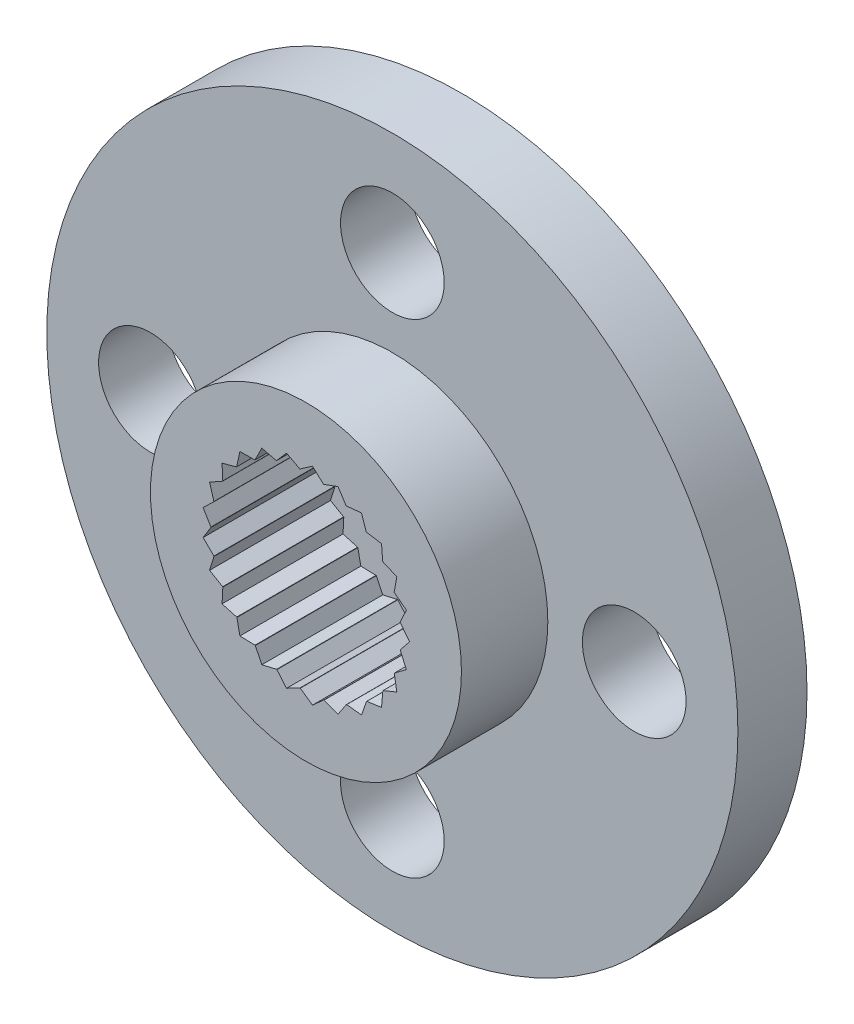
SolidWorks part; units mm, degrees
ref_plane "Front Plane" through (0, 0, 0) normal (0, 0, 1) x (1, 0, 0)
ref_plane "Top Plane" through (0, 0, 0) normal (0, 1, 0) x (1, 0, 0)
ref_plane "Right Plane" through (0, 0, 0) normal (1, 0, 0) x (0, 0, -1)
sketch "Sketch1" plane through (0, 0, 0) normal (0, 0, 1) x (1, 0, 0)
  circle A0 centre (0, 0) radius 10
  circle A1 centre (0, 0) radius 7 construction
  circle A2 centre (0, 7) radius 1.5
  circle A3 centre (7, 0) radius 1.5
  circle A4 centre (0, -7) radius 1.5
  circle A5 centre (-7, 0) radius 1.5
  circle A6 centre (0, 0) radius 4.5
  dimension "D1" = 20
  dimension "D2" = 3
  dimension "D3" = 4
extrude "Boss-Extrude1" add sketch "Sketch1" along normal blind 2
extrude "Boss-Extrude2" add sketch "Sketch1<2>" along normal blind 4.5 contours A6 region at (0, 0, 0)
sketch "Sketch1<2>" plane through (0, 0, 0) normal (0, 0, 1) x (1, 0, 0) same geometry as "Sketch1"
sketch "Sketch2" plane through (0, 0, 0) normal (0, 0, -1) x (-1, 0, 0)
  circle A0 centre (0, 0) radius 1.5
extrude "Cut-Extrude1" cut sketch "Sketch2" against normal blind 4.5
sketch "Sketch3" plane through (0, 0, 4.5) normal (0, 0, 1) x (1, 0, 0)
  circle A0 centre (0, 0) radius 2.75
extrude "Cut-Extrude2" cut sketch "Sketch3" against normal blind 3.5
sketch "Sketch4" plane through (0, 0, 4.5) normal (0, 0, 1) x (1, 0, 0)
  line L0 (0, 0) -> (-3, 0)
  line L1 (0, 0) -> (-2.9763, 0.376)
  line L2 (0, 0) -> (-2.9083, 0.7359)
  line L3 (-2.75, 0) -> (-2.9763, 0.376)
  line L4 (-2.666, 0.6746) -> (-2.9763, 0.376)
  circle A0 centre (0, 0) radius 3
  circle A1 centre (0, 0) radius 2.75 construction
  circle A2 centre (0, 0) radius 2.75 construction
  circle A3 centre (0, 0) radius 2.75
  circle M6 centre (0, 0) radius 2.75
  dimension "D1" = 7.2
  dimension "D2" = 14.2
extrude "Cut-Extrude3" cut sketch "Sketch4" against normal blind 3.5 contours L4 L1 M6 | L3 L1 M6 region at (-2.8205, 0.2422, 4.5) region at (-2.7928, 0.4638, 4.5)
pattern_circular "CirPattern1" count 25 over 360 about axis through (0, 0, 4.5) along (0, 0, -1) of "Cut-Extrude3" reverse direction yes
ref_axis "Motor Axis" through (0, 0, 13.7756) along (0, 0, -1)
